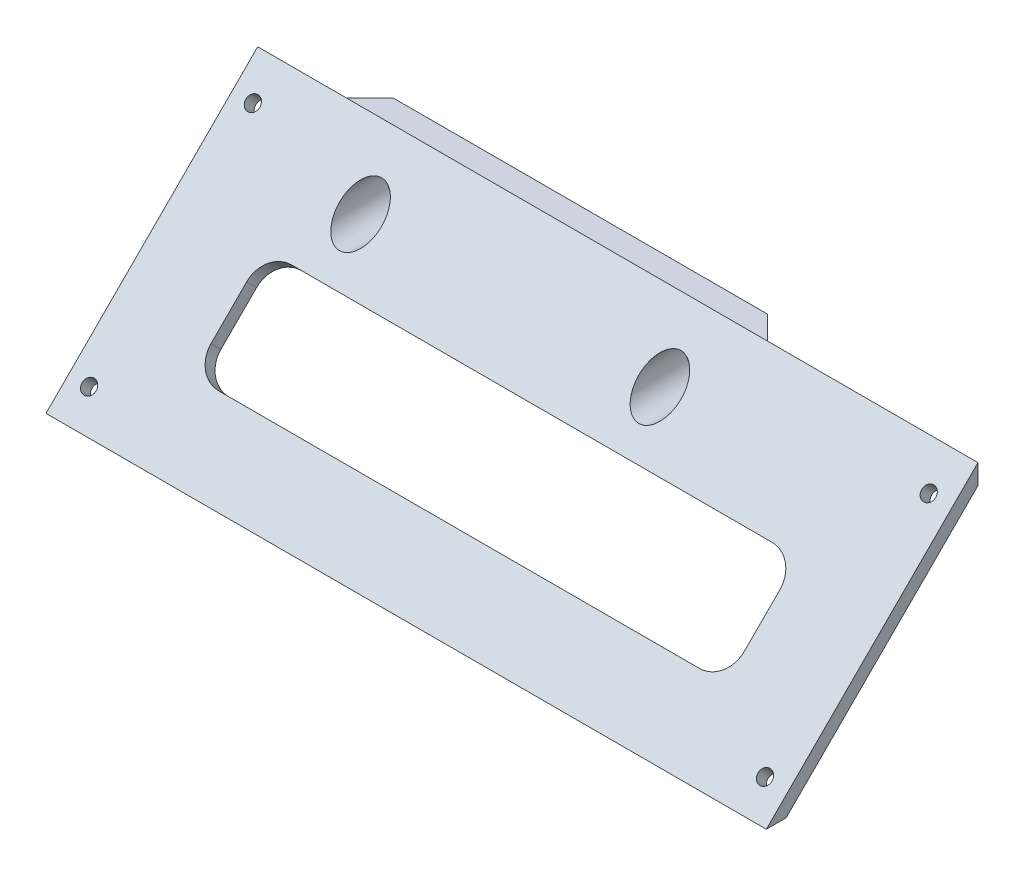
SolidWorks part; units mm, degrees
ref_plane "Front Plane" through (0, 0, 0) normal (0, 0, 1) x (1, 0, 0)
ref_plane "Top Plane" through (0, 0, 0) normal (0, 1, 0) x (1, 0, 0)
ref_plane "Right Plane" through (0, 0, 0) normal (1, 0, 0) x (0, 0, -1)
sketch "Sketch1" plane through (0, 0, 0) normal (0, 0, 1) x (1, 0, 0)
  line L1 (-40, -10) -> (40, -10)
  line L2 (-40, -10) -> (-40, 10)
  line L3 (-40, 10) -> (40, 10)
  line L4 (40, -10) -> (40, 10)
  line L5 (-40, -10) -> (40, 10) construction
  line L6 (-40, 10) -> (40, -10) construction
  point P0 (0, 0)
  dimension "D1" = 20
  dimension "D2" = 80
extrude "Boss-Extrude1" add sketch "Sketch1" along normal blind 5
sketch "Sketch3" plane through (0, 0, 0) normal (1, 0, 0) x (0, 0, -1)
  line L0 (-5, 10) -> (-50.2548, -35.2548)
  line L4 (-50.2548, -35.2548) -> (-46.0122, -35.2548)
  line L5 (-46.0122, -35.2548) -> (-5, 5.7574)
  line L6 (-5, -10) -> (-5, 10) construction
  line L7 (-5, 5.7574) -> (-5, 10)
  dimension "D1" = 3
  dimension "D2" = 45
  dimension "D3" = 64
extrude "Boss-Extrude2" add sketch "Sketch3" against normal blind 64 and the other way blind 90
sketch "Sketch4" plane through (0, 5.3787, 5.3787) normal (0, -0.7071, -0.7071) x (1, 0, 0)
  line L0 (-64, 57.4645) -> (-64, -0.5355) construction
  line L1 (70, 44.4645) -> (-44, 44.4645)
  line L2 (70, 44.4645) -> (70, 22.4645)
  line L3 (70, 22.4645) -> (-44, 22.4645)
  line L4 (-44, 44.4645) -> (-44, 22.4645)
  line L5 (70, 44.4645) -> (-44, 22.4645) construction
  line L6 (70, 22.4645) -> (-44, 44.4645) construction
  line L7 (90, 57.4645) -> (90, -0.5355) construction
  line L8 (90, 57.4645) -> (-64, 57.4645) construction
  point P0 (13, 33.4645)
  dimension "D1" = 20
  dimension "D2" = 20
  dimension "D3" = 13
  dimension "D4" = 22
extrude "Cut-Extrude2" cut sketch "Sketch4" against normal through all
chamfer "Chamfer1" distance 5 angle 45 2 edges at (40, 7.8787, 5) (-40, 7.8787, 5)
chamfer "Chamfer2" distance 11.3 angle 90 1 edges at (0, 5.7574, 5) first distance on face at (13, -18.2843, 29.0416)
chamfer "Chamfer4" distance 5 angle 65 1 edges at (0, -2.2329, 12.9903) first distance on face at (0, -6.1165, 9.1068)
ref_plane "Plane1" through (0, 0, 5) normal (0, 0, -1) x (-1, 0, 0)
sketch "Sketch2" plane through (0, 0, 0) normal (0, 0, 1) x (1, 0, 0)
  circle A0 centre (-32, 0) radius 2.3
  circle A1 centre (32, 0) radius 2.3
  dimension "D3" = 4.6
  dimension "D1" = 32
  dimension "D2" = 32
extrude "Cut-Extrude1" cut sketch "Sketch2" against normal through all and the other way through all
sketch "Sketch5" plane through (0, 0, 5) normal (0, 0, -1) x (-1, 0, 0)
  circle A0 centre (-32, 0) radius 4.5
  circle A1 centre (32, 0) radius 4.5
  dimension "D1" = 9
extrude "Cut-Extrude3" cut sketch "Sketch5" against normal through all
sketch "Sketch6" plane through (0, 7.5, 7.5) normal (0, 0.7071, 0.7071) x (1, 0, 0)
  circle A0 centre (-59.55, -4.2145) radius 1.5
  circle A1 centre (-59.55, -53.7145) radius 1.5
  circle A2 centre (84.95, -53.7145) radius 1.5
  circle A3 centre (84.95, -4.2145) radius 1.5
  dimension "D1" = 3
extrude "Cut-Extrude4" cut sketch "Sketch6" against normal blind 5
fillet "Fillet2" radius 5.6 4 edges at (70, -9.4454, 22.3241) (70, -25.0018, 37.8805) (-44, -25.0018, 37.8805) (-44, -9.4454, 22.3241)
